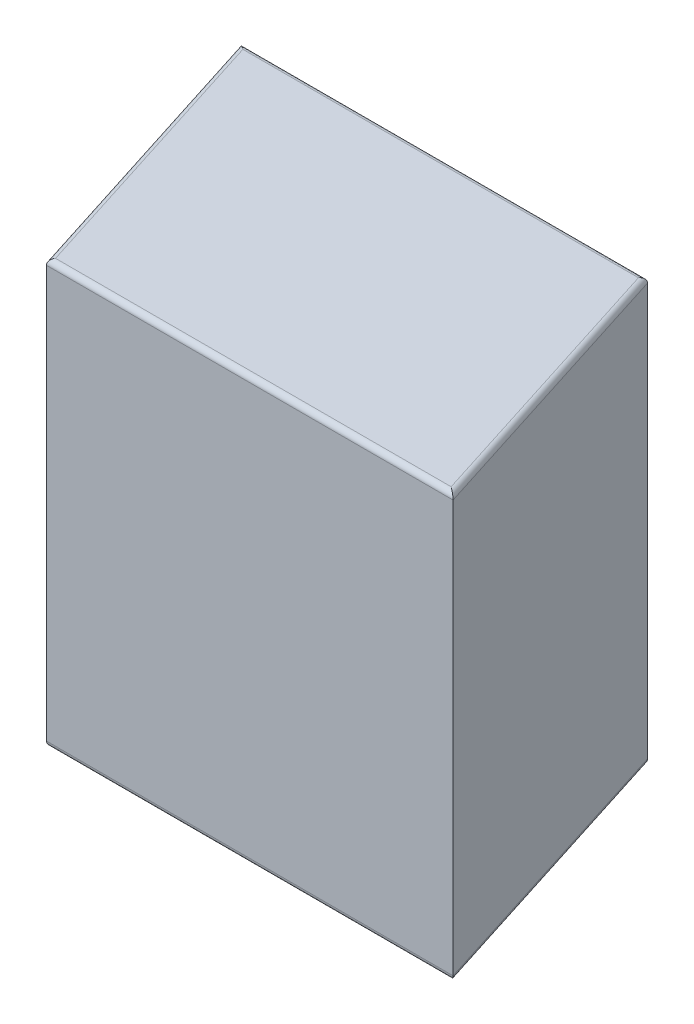
SolidWorks part; units mm, degrees
ref_plane "Front Plane" through (0, 0, 0) normal (0, 0, 1) x (1, 0, 0)
ref_plane "Top Plane" through (0, 0, 0) normal (0, 1, 0) x (1, 0, 0)
ref_plane "Right Plane" through (0, 0, 0) normal (1, 0, 0) x (0, 0, -1)
sketch "Sketch1" plane through (0, 0, 0) normal (0, 1, 0) x (1, 0, 0)
  line L4 (0, 0) -> (0, 28.6031) construction
  line L5 (0, 0) -> (26.1999, 0) construction
  line L6 (0, 0) -> (38.5, 0)
  line L7 (0, 0) -> (-8.5857, 27)
  line L8 (38.5, 0) -> (29.9143, 27)
  line L9 (-8.5857, 27) -> (29.9143, 27)
  dimension "D2" = 27
  dimension "D3" = 107.64
  dimension "D1" = 38.5
extrude "Boss-Extrude1" add sketch "Sketch1" along normal blind 40
fillet "Fillet1" radius 0.5 8 edges at (19.25, 0, 0) (34.2072, 0, -13.5) (10.6643, 0, -27) (-4.2928, 0, -13.5) (10.6643, 40, -27) (34.2072, 40, -13.5) (19.25, 40, 0) (-4.2928, 40, -13.5)
